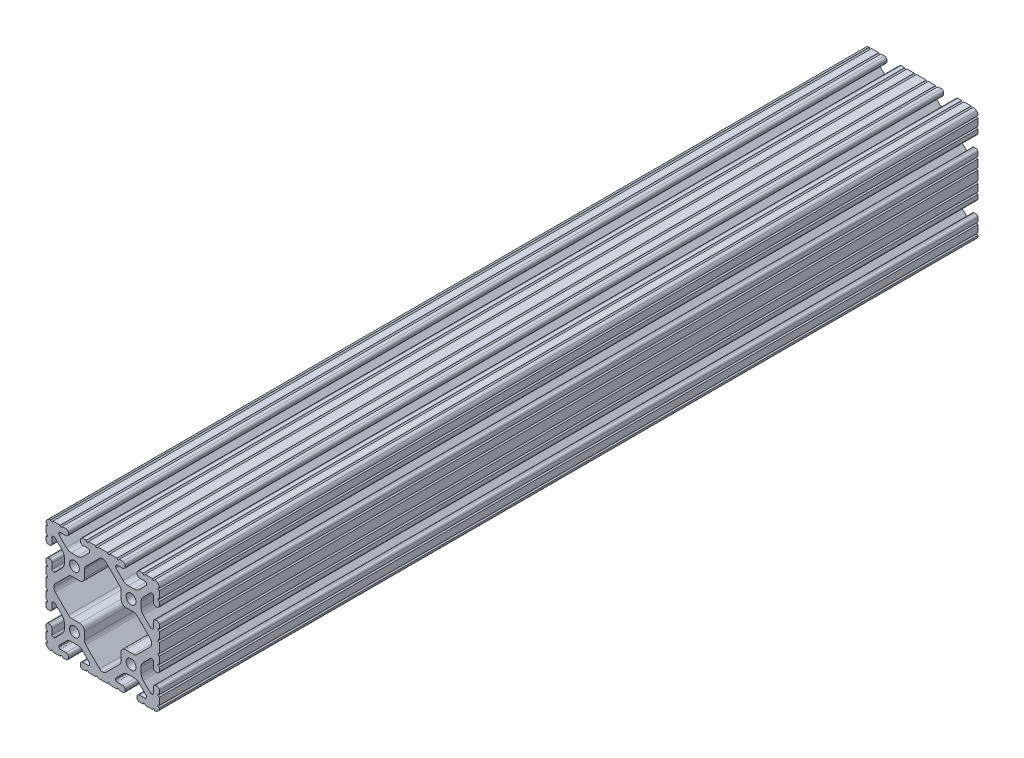
SolidWorks part; units mm, degrees
ref_plane "Front Plane" through (0, 0, 0) normal (0, 0, 1) x (1, 0, 0)
ref_plane "Top Plane" through (0, 0, 0) normal (0, 1, 0) x (1, 0, 0)
ref_plane "Right Plane" through (0, 0, 0) normal (1, 0, 0) x (0, 0, -1)
sketch "Sketch1" plane through (0, 0, 0) normal (0, 0, 1) x (1, 0, 0)
  line L0 (0, 38.1) -> (0, -38.1) construction
  line L1 (-38.1, -38.1) -> (38.1, -38.1) construction
  line L2 (-38.1, -38.1) -> (-38.1, 38.1) construction
  line L3 (-38.1, 38.1) -> (38.1, 38.1) construction
  line L4 (38.1, -38.1) -> (38.1, 38.1) construction
  line L5 (0, 38.1) -> (0, -38.1) construction
  line L6 (-38.1, 0) -> (38.1, 0) construction
  line L7 (-19.05, 19.05) -> (19.05, 19.05) construction
  line L8 (-19.05, 19.05) -> (-19.05, -19.05) construction
  line L9 (-19.05, -19.05) -> (19.05, -19.05) construction
  line L10 (19.05, 19.05) -> (19.05, -19.05) construction
  line L11 (-23.114, 38.1) -> (-23.114, -38.1) construction
  line L12 (-23.114, -38.1) -> (-14.986, 38.1) construction
  line L13 (-14.986, 38.1) -> (-14.986, -38.1) construction
  circle A0 centre (19.05, 19.05) radius 3.3274
  point P0 (0, 0)
  point P9 (0, 0)
  point P12 (-19.05, 0)
  line B0 (-11.3637, -22.8433) -> (-2.0515, -32.1555)
  line B1 (-12.2936, -15.4686) -> (-12.2936, -20.5983)
  line B2 (-20.769, -12.2936) -> (-15.4686, -12.2936)
  line B3 (-31.9021, -2.4756) -> (-23.0141, -11.3637)
  line B4 (-23.0141, 11.3637) -> (-31.9021, 2.4756)
  line B5 (-15.4686, 12.2936) -> (-20.769, 12.2936)
  line B6 (-12.2936, 20.5983) -> (-12.2936, 15.4686)
  line B7 (-2.0515, 32.1555) -> (-11.3637, 22.8433)
  line B8 (11.3637, 22.8433) -> (2.0515, 32.1555)
  line B9 (12.2936, 15.4686) -> (12.2936, 20.5983)
  line B10 (20.769, 12.2936) -> (15.4686, 12.2936)
  line B11 (31.9021, 2.4756) -> (23.0141, 11.3637)
  line B12 (23.0141, -11.3637) -> (31.9021, -2.4756)
  line B13 (15.4686, -12.2936) -> (20.769, -12.2936)
  line B14 (12.2936, -20.5983) -> (12.2936, -15.4686)
  line B15 (2.0515, -32.1555) -> (11.3637, -22.8433)
  line B16 (-4.7773, 38.1) -> (-9.6053, 38.1)
  line B17 (-11.1289, 38.1) -> (-13.4112, 38.1)
  line B18 (-14.986, 36.5252) -> (-14.986, 35.6108)
  line B19 (-13.4112, 34.036) -> (-9.652, 34.036)
  line B20 (-8.763, 33.147) -> (-8.763, 32.4935)
  line B21 (-9.0234, 31.8649) -> (-13.6907, 27.1976)
  line B22 (-17.0493, 25.8064) -> (-21.0507, 25.8064)
  line B23 (-24.4093, 27.1976) -> (-29.1002, 31.8885)
  line B24 (-29.337, 32.7207) -> (-29.337, 33.147)
  line B25 (-28.448, 34.036) -> (-24.6888, 34.036)
  line B26 (-23.114, 35.6108) -> (-23.114, 36.5252)
  line B27 (-24.6888, 38.1) -> (-27.0772, 38.1)
  line B28 (-28.6011, 38.1) -> (-33.4288, 38.1)
  line B29 (-38.1, 33.373) -> (-38.1, 28.5453)
  line B30 (-38.1, 27.0238) -> (-38.1, 24.6302)
  line B31 (-36.5252, 23.0554) -> (-35.6108, 23.0554)
  line B32 (-34.036, 24.6302) -> (-34.036, 28.448)
  line B33 (-33.147, 29.337) -> (-32.6643, 29.337)
  line B34 (-32.0357, 29.0766) -> (-27.1976, 24.2385)
  line B35 (-25.8064, 20.8799) -> (-25.8064, 17.2201)
  line B36 (-27.1976, 13.8615) -> (-31.9489, 9.1101)
  line B37 (-32.7869, 8.763) -> (-33.0603, 8.763)
  line B38 (-34.036, 9.7387) -> (-34.036, 13.4698)
  line B39 (-35.6108, 15.0446) -> (-36.5252, 15.0446)
  line B40 (-38.1, 13.4698) -> (-38.1, 11.075)
  line B41 (-38.1, 9.552) -> (-38.1, 4.7238)
  line B42 (-38.1, 3.2007) -> (-38.1, -3.2007)
  line B43 (-38.1, -4.7238) -> (-38.1, -9.552)
  line B44 (-38.1, -11.075) -> (-38.1, -13.4698)
  line B45 (-36.5252, -15.0446) -> (-35.6108, -15.0446)
  line B46 (-34.036, -13.4698) -> (-34.036, -9.7387)
  line B47 (-33.0603, -8.763) -> (-32.7869, -8.763)
  line B48 (-31.9489, -9.1101) -> (-27.1976, -13.8615)
  line B49 (-25.8064, -17.2201) -> (-25.8064, -20.8799)
  line B50 (-27.1976, -24.2385) -> (-32.0357, -29.0766)
  line B51 (-32.6643, -29.337) -> (-33.147, -29.337)
  line B52 (-34.036, -28.448) -> (-34.036, -24.6302)
  line B53 (-35.6108, -23.0554) -> (-36.5252, -23.0554)
  line B54 (-38.1, -24.6302) -> (-38.1, -27.0238)
  line B55 (-38.1, -28.5453) -> (-38.1, -33.373)
  line B56 (-33.4288, -38.1) -> (-28.6011, -38.1)
  line B57 (-27.0772, -38.1) -> (-24.6888, -38.1)
  line B58 (-23.114, -36.5252) -> (-23.114, -35.6108)
  line B59 (-24.6888, -34.036) -> (-28.448, -34.036)
  line B60 (-29.337, -33.147) -> (-29.337, -32.7207)
  line B61 (-29.1002, -31.8885) -> (-24.4093, -27.1976)
  line B62 (-21.0507, -25.8064) -> (-17.0493, -25.8064)
  line B63 (-13.6907, -27.1976) -> (-9.0234, -31.8649)
  line B64 (-8.763, -32.4935) -> (-8.763, -33.147)
  line B65 (-9.652, -34.036) -> (-13.4112, -34.036)
  line B66 (-14.986, -35.6108) -> (-14.986, -36.5252)
  line B67 (-13.4112, -38.1) -> (-11.1289, -38.1)
  line B68 (-9.6053, -38.1) -> (-4.7773, -38.1)
  line B69 (-3.2537, -38.1) -> (3.2537, -38.1)
  line B70 (4.7773, -38.1) -> (9.6053, -38.1)
  line B71 (11.1289, -38.1) -> (13.4112, -38.1)
  line B72 (14.986, -36.5252) -> (14.986, -35.6108)
  line B73 (13.4112, -34.036) -> (9.652, -34.036)
  line B74 (8.763, -33.147) -> (8.763, -32.4935)
  line B75 (9.0234, -31.8649) -> (13.6907, -27.1976)
  line B76 (17.0493, -25.8064) -> (21.0507, -25.8064)
  line B77 (24.4093, -27.1976) -> (29.1002, -31.8885)
  line B78 (29.337, -32.7207) -> (29.337, -33.147)
  line B79 (28.448, -34.036) -> (24.6888, -34.036)
  line B80 (23.114, -35.6108) -> (23.114, -36.5252)
  line B81 (24.6888, -38.1) -> (27.0772, -38.1)
  line B82 (28.6011, -38.1) -> (33.4288, -38.1)
  line B83 (38.1, -33.373) -> (38.1, -28.5453)
  line B84 (38.1, -27.0238) -> (38.1, -24.6302)
  line B85 (36.5252, -23.0554) -> (35.6108, -23.0554)
  line B86 (34.036, -24.6302) -> (34.036, -28.448)
  line B87 (33.147, -29.337) -> (32.6643, -29.337)
  line B88 (32.0357, -29.0766) -> (27.1976, -24.2385)
  line B89 (25.8064, -20.8799) -> (25.8064, -17.2201)
  line B90 (27.1976, -13.8615) -> (31.9489, -9.1101)
  line B91 (32.7869, -8.763) -> (33.0603, -8.763)
  line B92 (34.036, -9.7387) -> (34.036, -13.4698)
  line B93 (35.6108, -15.0446) -> (36.5252, -15.0446)
  line B94 (38.1, -13.4698) -> (38.1, -11.075)
  line B95 (38.1, -9.552) -> (38.1, -4.7238)
  line B96 (38.1, -3.2007) -> (38.1, 3.2007)
  line B97 (38.1, 4.7238) -> (38.1, 9.552)
  line B98 (38.1, 11.075) -> (38.1, 13.4698)
  line B99 (36.5252, 15.0446) -> (35.6108, 15.0446)
  line B100 (34.036, 13.4698) -> (34.036, 9.7387)
  line B101 (33.0603, 8.763) -> (32.7869, 8.763)
  line B102 (31.9489, 9.1101) -> (27.1976, 13.8615)
  line B103 (25.8064, 17.2201) -> (25.8064, 20.8799)
  line B104 (27.1976, 24.2385) -> (32.0357, 29.0766)
  line B105 (32.6643, 29.337) -> (33.147, 29.337)
  line B106 (34.036, 28.448) -> (34.036, 24.6302)
  line B107 (35.6108, 23.0554) -> (36.5252, 23.0554)
  line B108 (38.1, 24.6302) -> (38.1, 27.0238)
  line B109 (38.1, 28.5453) -> (38.1, 33.373)
  line B110 (33.4288, 38.1) -> (28.6011, 38.1)
  line B111 (27.0772, 38.1) -> (24.6888, 38.1)
  line B112 (23.114, 36.5252) -> (23.114, 35.6108)
  line B113 (24.6888, 34.036) -> (28.448, 34.036)
  line B114 (29.337, 33.147) -> (29.337, 32.7207)
  line B115 (29.1002, 31.8885) -> (24.4093, 27.1976)
  line B116 (21.0507, 25.8064) -> (17.0493, 25.8064)
  line B117 (13.6907, 27.1976) -> (9.0234, 31.8649)
  line B118 (8.763, 32.4935) -> (8.763, 33.147)
  line B119 (9.652, 34.036) -> (13.4112, 34.036)
  line B120 (14.986, 35.6108) -> (14.986, 36.5252)
  line B121 (13.4112, 38.1) -> (11.1289, 38.1)
  line B122 (9.6053, 38.1) -> (4.7773, 38.1)
  line B123 (3.2537, 38.1) -> (-3.2537, 38.1)
  circle B124 centre (-19.05, 19.05) radius 3.3274
  circle B125 centre (-19.05, -19.05) radius 3.3274
  circle B126 centre (19.05, -19.05) radius 3.3274
  circle B127 centre (19.05, 19.05) radius 3.3274
  arc B128 (0, -33.011) -> (2.0515, -32.1555) centre (-0.0139, -30.09) ccw
  arc B129 (-2.0515, -32.1555) -> (0, -33.011) centre (0.0139, -30.09) ccw
  arc B130 (-12.2936, -20.5983) -> (-11.3637, -22.8433) centre (-9.1186, -20.5983) ccw
  arc B131 (-12.2936, -15.4686) -> (-15.4686, -12.2936) centre (-15.4686, -15.4686) ccw
  arc B132 (-23.0141, -11.3637) -> (-20.769, -12.2936) centre (-20.769, -9.1186) ccw
  arc B133 (-32.7287, 0) -> (-31.9021, -2.4756) centre (-29.8367, -0.4102) ccw
  arc B134 (-31.9021, 2.4756) -> (-32.7287, 0) centre (-29.8367, 0.4102) ccw
  arc B135 (-20.769, 12.2936) -> (-23.0141, 11.3637) centre (-20.769, 9.1186) ccw
  arc B136 (-15.4686, 12.2936) -> (-12.2936, 15.4686) centre (-15.4686, 15.4686) ccw
  arc B137 (-11.3637, 22.8433) -> (-12.2936, 20.5983) centre (-9.1186, 20.5983) ccw
  arc B138 (0, 33.011) -> (-2.0515, 32.1555) centre (0.0139, 30.09) ccw
  arc B139 (2.0515, 32.1555) -> (0, 33.011) centre (-0.0139, 30.09) ccw
  arc B140 (12.2936, 20.5983) -> (11.3637, 22.8433) centre (9.1186, 20.5983) ccw
  arc B141 (12.2936, 15.4686) -> (15.4686, 12.2936) centre (15.4686, 15.4686) ccw
  arc B142 (23.0141, 11.3637) -> (20.769, 12.2936) centre (20.769, 9.1186) ccw
  arc B143 (32.7287, 0) -> (31.9021, 2.4756) centre (29.8367, 0.4102) ccw
  arc B144 (31.9021, -2.4756) -> (32.7287, 0) centre (29.8367, -0.4102) ccw
  arc B145 (20.769, -12.2936) -> (23.0141, -11.3637) centre (20.769, -9.1186) ccw
  arc B146 (15.4686, -12.2936) -> (12.2936, -15.4686) centre (15.4686, -15.4686) ccw
  arc B147 (11.3637, -22.8433) -> (12.2936, -20.5983) centre (9.1186, -20.5983) ccw
  arc B148 (-4.7773, 38.1) -> (-3.2537, 38.1) centre (-4.0155, 38.0824) ccw
  arc B149 (-11.1289, 38.1) -> (-9.6053, 38.1) centre (-10.3671, 38.0824) ccw
  arc B150 (-13.4112, 38.1) -> (-14.986, 36.5252) centre (-13.4112, 36.5252) ccw
  arc B151 (-14.986, 35.6108) -> (-13.4112, 34.036) centre (-13.4112, 35.6108) ccw
  arc B152 (-8.763, 33.147) -> (-9.652, 34.036) centre (-9.652, 33.147) ccw
  arc B153 (-9.0234, 31.8649) -> (-8.763, 32.4935) centre (-9.652, 32.4935) ccw
  arc B154 (-17.0493, 25.8064) -> (-13.6907, 27.1976) centre (-17.0493, 30.5562) ccw
  arc B155 (-24.4093, 27.1976) -> (-21.0507, 25.8064) centre (-21.0507, 30.5562) ccw
  arc B156 (-29.337, 32.7207) -> (-29.1002, 31.8885) centre (-28.4716, 32.5172) ccw
  arc B157 (-28.448, 34.036) -> (-29.337, 33.147) centre (-28.448, 33.147) ccw
  arc B158 (-24.6888, 34.036) -> (-23.114, 35.6108) centre (-24.6888, 35.6108) ccw
  arc B159 (-23.114, 36.5252) -> (-24.6888, 38.1) centre (-24.6888, 36.5252) ccw
  arc B160 (-28.6011, 38.1) -> (-27.0772, 38.1) centre (-27.8392, 38.0824) ccw
  arc B161 (-34.9527, 38.1) -> (-33.4288, 38.1) centre (-34.1907, 38.0824) ccw
  arc B162 (-34.9527, 38.1) -> (-37.0861, 37.1826) centre (-34.8521, 34.9266) ccw
  arc B163 (-37.0861, 37.1826) -> (-38.1, 34.8455) centre (-34.925, 34.8566) ccw
  arc B164 (-38.1, 33.373) -> (-38.1, 34.8455) centre (-37.9035, 34.1092) ccw
  arc B165 (-38.1, 27.0238) -> (-38.1, 28.5453) centre (-37.9035, 27.7845) ccw
  arc B166 (-38.1, 24.6302) -> (-36.5252, 23.0554) centre (-36.5252, 24.6302) ccw
  arc B167 (-35.6108, 23.0554) -> (-34.036, 24.6302) centre (-35.6108, 24.6302) ccw
  arc B168 (-33.147, 29.337) -> (-34.036, 28.448) centre (-33.147, 28.448) ccw
  arc B169 (-32.0357, 29.0766) -> (-32.6643, 29.337) centre (-32.6643, 28.448) ccw
  arc B170 (-25.8064, 20.8799) -> (-27.1976, 24.2385) centre (-30.5562, 20.8799) ccw
  arc B171 (-27.1976, 13.8615) -> (-25.8064, 17.2201) centre (-30.5562, 17.2201) ccw
  arc B172 (-32.7869, 8.763) -> (-31.9489, 9.1101) centre (-32.7869, 9.9481) ccw
  arc B173 (-34.036, 9.7387) -> (-33.0603, 8.763) centre (-33.0603, 9.7387) ccw
  arc B174 (-34.036, 13.4698) -> (-35.6108, 15.0446) centre (-35.6108, 13.4698) ccw
  arc B175 (-36.5252, 15.0446) -> (-38.1, 13.4698) centre (-36.5252, 13.4698) ccw
  arc B176 (-38.1, 9.552) -> (-38.1, 11.075) centre (-37.9035, 10.3135) ccw
  arc B177 (-38.1, 3.2007) -> (-38.1, 4.7238) centre (-37.9035, 3.9622) ccw
  arc B178 (-38.1, -4.7238) -> (-38.1, -3.2007) centre (-37.9035, -3.9622) ccw
  arc B179 (-38.1, -11.075) -> (-38.1, -9.552) centre (-37.9035, -10.3135) ccw
  arc B180 (-38.1, -13.4698) -> (-36.5252, -15.0446) centre (-36.5252, -13.4698) ccw
  arc B181 (-35.6108, -15.0446) -> (-34.036, -13.4698) centre (-35.6108, -13.4698) ccw
  arc B182 (-33.0603, -8.763) -> (-34.036, -9.7387) centre (-33.0603, -9.7387) ccw
  arc B183 (-31.9489, -9.1101) -> (-32.7869, -8.763) centre (-32.7869, -9.9481) ccw
  arc B184 (-25.8064, -17.2201) -> (-27.1976, -13.8615) centre (-30.5562, -17.2201) ccw
  arc B185 (-27.1976, -24.2385) -> (-25.8064, -20.8799) centre (-30.5562, -20.8799) ccw
  arc B186 (-32.6643, -29.337) -> (-32.0357, -29.0766) centre (-32.6643, -28.448) ccw
  arc B187 (-34.036, -28.448) -> (-33.147, -29.337) centre (-33.147, -28.448) ccw
  arc B188 (-34.036, -24.6302) -> (-35.6108, -23.0554) centre (-35.6108, -24.6302) ccw
  arc B189 (-36.5252, -23.0554) -> (-38.1, -24.6302) centre (-36.5252, -24.6302) ccw
  arc B190 (-38.1, -28.5453) -> (-38.1, -27.0238) centre (-37.9035, -27.7845) ccw
  arc B191 (-38.1, -34.8455) -> (-38.1, -33.373) centre (-37.9035, -34.1092) ccw
  arc B192 (-38.1, -34.8455) -> (-37.0861, -37.1826) centre (-34.925, -34.8566) ccw
  arc B193 (-37.0861, -37.1826) -> (-34.9527, -38.1) centre (-34.8521, -34.9266) ccw
  arc B194 (-33.4288, -38.1) -> (-34.9527, -38.1) centre (-34.1907, -38.0824) ccw
  arc B195 (-27.0772, -38.1) -> (-28.6011, -38.1) centre (-27.8392, -38.0824) ccw
  arc B196 (-24.6888, -38.1) -> (-23.114, -36.5252) centre (-24.6888, -36.5252) ccw
  arc B197 (-23.114, -35.6108) -> (-24.6888, -34.036) centre (-24.6888, -35.6108) ccw
  arc B198 (-29.337, -33.147) -> (-28.448, -34.036) centre (-28.448, -33.147) ccw
  arc B199 (-29.1002, -31.8885) -> (-29.337, -32.7207) centre (-28.4716, -32.5172) ccw
  arc B200 (-21.0507, -25.8064) -> (-24.4093, -27.1976) centre (-21.0507, -30.5562) ccw
  arc B201 (-13.6907, -27.1976) -> (-17.0493, -25.8064) centre (-17.0493, -30.5562) ccw
  arc B202 (-8.763, -32.4935) -> (-9.0234, -31.8649) centre (-9.652, -32.4935) ccw
  arc B203 (-9.652, -34.036) -> (-8.763, -33.147) centre (-9.652, -33.147) ccw
  arc B204 (-13.4112, -34.036) -> (-14.986, -35.6108) centre (-13.4112, -35.6108) ccw
  arc B205 (-14.986, -36.5252) -> (-13.4112, -38.1) centre (-13.4112, -36.5252) ccw
  arc B206 (-9.6053, -38.1) -> (-11.1289, -38.1) centre (-10.3671, -38.0824) ccw
  arc B207 (-3.2537, -38.1) -> (-4.7773, -38.1) centre (-4.0155, -38.0824) ccw
  arc B208 (4.7773, -38.1) -> (3.2537, -38.1) centre (4.0155, -38.0824) ccw
  arc B209 (11.1289, -38.1) -> (9.6053, -38.1) centre (10.3671, -38.0824) ccw
  arc B210 (13.4112, -38.1) -> (14.986, -36.5252) centre (13.4112, -36.5252) ccw
  arc B211 (14.986, -35.6108) -> (13.4112, -34.036) centre (13.4112, -35.6108) ccw
  arc B212 (8.763, -33.147) -> (9.652, -34.036) centre (9.652, -33.147) ccw
  arc B213 (9.0234, -31.8649) -> (8.763, -32.4935) centre (9.652, -32.4935) ccw
  arc B214 (17.0493, -25.8064) -> (13.6907, -27.1976) centre (17.0493, -30.5562) ccw
  arc B215 (24.4093, -27.1976) -> (21.0507, -25.8064) centre (21.0507, -30.5562) ccw
  arc B216 (29.337, -32.7207) -> (29.1002, -31.8885) centre (28.4716, -32.5172) ccw
  arc B217 (28.448, -34.036) -> (29.337, -33.147) centre (28.448, -33.147) ccw
  arc B218 (24.6888, -34.036) -> (23.114, -35.6108) centre (24.6888, -35.6108) ccw
  arc B219 (23.114, -36.5252) -> (24.6888, -38.1) centre (24.6888, -36.5252) ccw
  arc B220 (28.6011, -38.1) -> (27.0772, -38.1) centre (27.8392, -38.0824) ccw
  arc B221 (34.9527, -38.1) -> (33.4288, -38.1) centre (34.1907, -38.0824) ccw
  arc B222 (34.9527, -38.1) -> (37.0861, -37.1826) centre (34.8521, -34.9266) ccw
  arc B223 (37.0861, -37.1826) -> (38.1, -34.8455) centre (34.925, -34.8566) ccw
  arc B224 (38.1, -33.373) -> (38.1, -34.8455) centre (37.9035, -34.1092) ccw
  arc B225 (38.1, -27.0238) -> (38.1, -28.5453) centre (37.9035, -27.7845) ccw
  arc B226 (38.1, -24.6302) -> (36.5252, -23.0554) centre (36.5252, -24.6302) ccw
  arc B227 (35.6108, -23.0554) -> (34.036, -24.6302) centre (35.6108, -24.6302) ccw
  arc B228 (33.147, -29.337) -> (34.036, -28.448) centre (33.147, -28.448) ccw
  arc B229 (32.0357, -29.0766) -> (32.6643, -29.337) centre (32.6643, -28.448) ccw
  arc B230 (25.8064, -20.8799) -> (27.1976, -24.2385) centre (30.5562, -20.8799) ccw
  arc B231 (27.1976, -13.8615) -> (25.8064, -17.2201) centre (30.5562, -17.2201) ccw
  arc B232 (32.7869, -8.763) -> (31.9489, -9.1101) centre (32.7869, -9.9481) ccw
  arc B233 (34.036, -9.7387) -> (33.0603, -8.763) centre (33.0603, -9.7387) ccw
  arc B234 (34.036, -13.4698) -> (35.6108, -15.0446) centre (35.6108, -13.4698) ccw
  arc B235 (36.5252, -15.0446) -> (38.1, -13.4698) centre (36.5252, -13.4698) ccw
  arc B236 (38.1, -9.552) -> (38.1, -11.075) centre (37.9035, -10.3135) ccw
  arc B237 (38.1, -3.2007) -> (38.1, -4.7238) centre (37.9035, -3.9622) ccw
  arc B238 (38.1, 4.7238) -> (38.1, 3.2007) centre (37.9035, 3.9622) ccw
  arc B239 (38.1, 11.075) -> (38.1, 9.552) centre (37.9035, 10.3135) ccw
  arc B240 (38.1, 13.4698) -> (36.5252, 15.0446) centre (36.5252, 13.4698) ccw
  arc B241 (35.6108, 15.0446) -> (34.036, 13.4698) centre (35.6108, 13.4698) ccw
  arc B242 (33.0603, 8.763) -> (34.036, 9.7387) centre (33.0603, 9.7387) ccw
  arc B243 (31.9489, 9.1101) -> (32.7869, 8.763) centre (32.7869, 9.9481) ccw
  arc B244 (25.8064, 17.2201) -> (27.1976, 13.8615) centre (30.5562, 17.2201) ccw
  arc B245 (27.1976, 24.2385) -> (25.8064, 20.8799) centre (30.5562, 20.8799) ccw
  arc B246 (32.6643, 29.337) -> (32.0357, 29.0766) centre (32.6643, 28.448) ccw
  arc B247 (34.036, 28.448) -> (33.147, 29.337) centre (33.147, 28.448) ccw
  arc B248 (34.036, 24.6302) -> (35.6108, 23.0554) centre (35.6108, 24.6302) ccw
  arc B249 (36.5252, 23.0554) -> (38.1, 24.6302) centre (36.5252, 24.6302) ccw
  arc B250 (38.1, 28.5453) -> (38.1, 27.0238) centre (37.9035, 27.7845) ccw
  arc B251 (38.1, 34.8455) -> (38.1, 33.373) centre (37.9035, 34.1092) ccw
  arc B252 (38.1, 34.8455) -> (37.0861, 37.1826) centre (34.925, 34.8566) ccw
  arc B253 (37.0861, 37.1826) -> (34.9527, 38.1) centre (34.8521, 34.9266) ccw
  arc B254 (33.4288, 38.1) -> (34.9527, 38.1) centre (34.1907, 38.0824) ccw
  arc B255 (27.0772, 38.1) -> (28.6011, 38.1) centre (27.8392, 38.0824) ccw
  arc B256 (24.6888, 38.1) -> (23.114, 36.5252) centre (24.6888, 36.5252) ccw
  arc B257 (23.114, 35.6108) -> (24.6888, 34.036) centre (24.6888, 35.6108) ccw
  arc B258 (29.337, 33.147) -> (28.448, 34.036) centre (28.448, 33.147) ccw
  arc B259 (29.1002, 31.8885) -> (29.337, 32.7207) centre (28.4716, 32.5172) ccw
  arc B260 (21.0507, 25.8064) -> (24.4093, 27.1976) centre (21.0507, 30.5562) ccw
  arc B261 (13.6907, 27.1976) -> (17.0493, 25.8064) centre (17.0493, 30.5562) ccw
  arc B262 (8.763, 32.4935) -> (9.0234, 31.8649) centre (9.652, 32.4935) ccw
  arc B263 (9.652, 34.036) -> (8.763, 33.147) centre (9.652, 33.147) ccw
  arc B264 (13.4112, 34.036) -> (14.986, 35.6108) centre (13.4112, 35.6108) ccw
  arc B265 (14.986, 36.5252) -> (13.4112, 38.1) centre (13.4112, 36.5252) ccw
  arc B266 (9.6053, 38.1) -> (11.1289, 38.1) centre (10.3671, 38.0824) ccw
  arc B267 (3.2537, 38.1) -> (4.7773, 38.1) centre (4.0155, 38.0824) ccw
  dimension "Center Hole Diameter" = 6.6548
  dimension "Rail Width" = 76.2
  dimension "Rail Height" = 76.2
  dimension "T-Slot Width" = 8.128
sketch_block_instance "Block1-1"
sketch_block "Block1"
sketch "Sketch2" plane through (0, 0, 0) normal (1, 0, 0) x (0, 0, -1)
  line L0 (-275, 0) -> (275, 0) construction
  line L1 (-275, 38.1) -> (-275, -38.1) construction
  line L2 (-275, -38.1) -> (275, -38.1) construction
  line L3 (275, -38.1) -> (275, 38.1) construction
  line L4 (-173.4, 0) -> (-173.4, 38.1) construction
  line L5 (-173.4, 38.1) -> (173.4, 38.1) construction
  line L6 (173.4, 38.1) -> (173.4, 0) construction
  point P5 (173.4, 0)
  point P10 (-173.4, 0)
  dimension "D1" = 101.6
  dimension "Length" = 550
  dimension "D2" = 101.6
sketch "Sketch3" plane through (0, 0, 0) normal (0, 0, 1) x (1, 0, 0)
  line L0 (-11.3637, -22.8433) -> (-2.0515, -32.1555) construction
  line L1 (-12.2936, -15.4686) -> (-12.2936, -20.5983) construction
  line L2 (-20.769, -12.2936) -> (-15.4686, -12.2936) construction
  line L3 (-31.9021, -2.4756) -> (-23.0141, -11.3637) construction
  line L4 (-23.0141, 11.3637) -> (-31.9021, 2.4756) construction
  line L5 (-15.4686, 12.2936) -> (-20.769, 12.2936) construction
  line L6 (-12.2936, 20.5983) -> (-12.2936, 15.4686) construction
  line L7 (-2.0515, 32.1555) -> (-11.3637, 22.8433) construction
  line L8 (11.3637, 22.8433) -> (2.0515, 32.1555) construction
  line L9 (12.2936, 15.4686) -> (12.2936, 20.5983) construction
  line L10 (20.769, 12.2936) -> (15.4686, 12.2936) construction
  line L11 (31.9021, 2.4756) -> (23.0141, 11.3637) construction
  line L12 (23.0141, -11.3637) -> (31.9021, -2.4756) construction
  line L13 (15.4686, -12.2936) -> (20.769, -12.2936) construction
  line L14 (12.2936, -20.5983) -> (12.2936, -15.4686) construction
  line L15 (2.0515, -32.1555) -> (11.3637, -22.8433) construction
  line L16 (34.036, 28.448) -> (34.036, 24.6302) construction
  line L17 (35.6108, 23.0554) -> (36.5252, 23.0554) construction
  line L18 (38.1, 24.6302) -> (38.1, 27.0238) construction
  line L19 (38.1, 28.5453) -> (38.1, 33.373) construction
  line L20 (33.4288, 38.1) -> (28.6011, 38.1) construction
  line L21 (27.0772, 38.1) -> (24.6888, 38.1) construction
  line L22 (23.114, 36.5252) -> (23.114, 35.6108) construction
  line L23 (24.6888, 34.036) -> (28.448, 34.036) construction
  line L24 (29.337, 33.147) -> (29.337, 32.7207) construction
  line L25 (29.1002, 31.8885) -> (24.4093, 27.1976) construction
  line L26 (21.0507, 25.8064) -> (17.0493, 25.8064) construction
  line L27 (13.6907, 27.1976) -> (9.0234, 31.8649) construction
  line L28 (8.763, 32.4935) -> (8.763, 33.147) construction
  line L29 (9.652, 34.036) -> (13.4112, 34.036) construction
  line L30 (14.986, 35.6108) -> (14.986, 36.5252) construction
  line L31 (13.4112, 38.1) -> (11.1289, 38.1) construction
  line L32 (9.6053, 38.1) -> (4.7773, 38.1) construction
  line L33 (3.2537, 38.1) -> (-3.2537, 38.1) construction
  line L34 (-4.7773, 38.1) -> (-9.6053, 38.1) construction
  line L35 (-11.1289, 38.1) -> (-13.4112, 38.1) construction
  line L36 (-14.986, 36.5252) -> (-14.986, 35.6108) construction
  line L37 (-13.4112, 34.036) -> (-9.652, 34.036) construction
  line L38 (-8.763, 33.147) -> (-8.763, 32.4935) construction
  line L39 (-9.0234, 31.8649) -> (-13.6907, 27.1976) construction
  line L40 (-17.0493, 25.8064) -> (-21.0507, 25.8064) construction
  line L41 (-24.4093, 27.1976) -> (-29.1002, 31.8885) construction
  line L42 (-29.337, 32.7207) -> (-29.337, 33.147) construction
  line L43 (-28.448, 34.036) -> (-24.6888, 34.036) construction
  line L44 (-23.114, 35.6108) -> (-23.114, 36.5252) construction
  line L45 (-24.6888, 38.1) -> (-27.0772, 38.1) construction
  line L46 (-28.6011, 38.1) -> (-33.4288, 38.1) construction
  line L47 (-38.1, 33.373) -> (-38.1, 28.5453) construction
  line L48 (-38.1, 27.0238) -> (-38.1, 24.6302) construction
  line L49 (-36.5252, 23.0554) -> (-35.6108, 23.0554) construction
  line L50 (-34.036, 24.6302) -> (-34.036, 28.448) construction
  line L51 (-33.147, 29.337) -> (-32.6643, 29.337) construction
  line L52 (-32.0357, 29.0766) -> (-27.1976, 24.2385) construction
  line L53 (-25.8064, 20.8799) -> (-25.8064, 17.2201) construction
  line L54 (-27.1976, 13.8615) -> (-31.9489, 9.1101) construction
  line L55 (-32.7869, 8.763) -> (-33.0603, 8.763) construction
  line L56 (-34.036, 9.7387) -> (-34.036, 13.4698) construction
  line L57 (-35.6108, 15.0446) -> (-36.5252, 15.0446) construction
  line L58 (-38.1, 13.4698) -> (-38.1, 11.075) construction
  line L59 (-38.1, 9.552) -> (-38.1, 4.7238) construction
  line L60 (-38.1, 3.2007) -> (-38.1, -3.2007) construction
  line L61 (-38.1, -4.7238) -> (-38.1, -9.552) construction
  line L62 (-38.1, -11.075) -> (-38.1, -13.4698) construction
  line L63 (-36.5252, -15.0446) -> (-35.6108, -15.0446) construction
  line L64 (-34.036, -13.4698) -> (-34.036, -9.7387) construction
  line L65 (-33.0603, -8.763) -> (-32.7869, -8.763) construction
  line L66 (-31.9489, -9.1101) -> (-27.1976, -13.8615) construction
  line L67 (-25.8064, -17.2201) -> (-25.8064, -20.8799) construction
  line L68 (-27.1976, -24.2385) -> (-32.0357, -29.0766) construction
  line L69 (-32.6643, -29.337) -> (-33.147, -29.337) construction
  line L70 (-34.036, -28.448) -> (-34.036, -24.6302) construction
  line L71 (-35.6108, -23.0554) -> (-36.5252, -23.0554) construction
  line L72 (-38.1, -24.6302) -> (-38.1, -27.0238) construction
  line L73 (-38.1, -28.5453) -> (-38.1, -33.373) construction
  line L74 (-33.4288, -38.1) -> (-28.6011, -38.1) construction
  line L75 (-27.0772, -38.1) -> (-24.6888, -38.1) construction
  line L76 (-23.114, -36.5252) -> (-23.114, -35.6108) construction
  line L77 (-24.6888, -34.036) -> (-28.448, -34.036) construction
  line L78 (-29.337, -33.147) -> (-29.337, -32.7207) construction
  line L79 (-29.1002, -31.8885) -> (-24.4093, -27.1976) construction
  line L80 (-21.0507, -25.8064) -> (-17.0493, -25.8064) construction
  line L81 (-13.6907, -27.1976) -> (-9.0234, -31.8649) construction
  line L82 (-8.763, -32.4935) -> (-8.763, -33.147) construction
  line L83 (-9.652, -34.036) -> (-13.4112, -34.036) construction
  line L84 (-14.986, -35.6108) -> (-14.986, -36.5252) construction
  line L85 (-13.4112, -38.1) -> (-11.1289, -38.1) construction
  line L86 (-9.6053, -38.1) -> (-4.7773, -38.1) construction
  line L87 (-3.2537, -38.1) -> (3.2537, -38.1) construction
  line L88 (4.7773, -38.1) -> (9.6053, -38.1) construction
  line L89 (11.1289, -38.1) -> (13.4112, -38.1) construction
  line L90 (14.986, -36.5252) -> (14.986, -35.6108) construction
  line L91 (13.4112, -34.036) -> (9.652, -34.036) construction
  line L92 (8.763, -33.147) -> (8.763, -32.4935) construction
  line L93 (9.0234, -31.8649) -> (13.6907, -27.1976) construction
  line L94 (17.0493, -25.8064) -> (21.0507, -25.8064) construction
  line L95 (24.4093, -27.1976) -> (29.1002, -31.8885) construction
  line L96 (29.337, -32.7207) -> (29.337, -33.147) construction
  line L97 (28.448, -34.036) -> (24.6888, -34.036) construction
  line L98 (23.114, -35.6108) -> (23.114, -36.5252) construction
  line L99 (24.6888, -38.1) -> (27.0772, -38.1) construction
  line L100 (28.6011, -38.1) -> (33.4288, -38.1) construction
  line L101 (38.1, -33.373) -> (38.1, -28.5453) construction
  line L102 (38.1, -27.0238) -> (38.1, -24.6302) construction
  line L103 (36.5252, -23.0554) -> (35.6108, -23.0554) construction
  line L104 (34.036, -24.6302) -> (34.036, -28.448) construction
  line L105 (33.147, -29.337) -> (32.6643, -29.337) construction
  line L106 (32.0357, -29.0766) -> (27.1976, -24.2385) construction
  line L107 (25.8064, -20.8799) -> (25.8064, -17.2201) construction
  line L108 (27.1976, -13.8615) -> (31.9489, -9.1101) construction
  line L109 (32.7869, -8.763) -> (33.0603, -8.763) construction
  line L110 (34.036, -9.7387) -> (34.036, -13.4698) construction
  line L111 (35.6108, -15.0446) -> (36.5252, -15.0446) construction
  line L112 (38.1, -13.4698) -> (38.1, -11.075) construction
  line L113 (38.1, -9.552) -> (38.1, -4.7238) construction
  line L114 (38.1, -3.2007) -> (38.1, 3.2007) construction
  line L115 (38.1, 4.7238) -> (38.1, 9.552) construction
  line L116 (38.1, 11.075) -> (38.1, 13.4698) construction
  line L117 (36.5252, 15.0446) -> (35.6108, 15.0446) construction
  line L118 (34.036, 13.4698) -> (34.036, 9.7387) construction
  line L119 (33.0603, 8.763) -> (32.7869, 8.763) construction
  line L120 (31.9489, 9.1101) -> (27.1976, 13.8615) construction
  line L121 (25.8064, 17.2201) -> (25.8064, 20.8799) construction
  line L122 (27.1976, 24.2385) -> (32.0357, 29.0766) construction
  line L123 (32.6643, 29.337) -> (33.147, 29.337) construction
  line L124 (-11.3637, -22.8433) -> (-2.0515, -32.1555)
  line L125 (-12.2936, -15.4686) -> (-12.2936, -20.5983)
  line L126 (-20.769, -12.2936) -> (-15.4686, -12.2936)
  line L127 (-31.9021, -2.4756) -> (-23.0141, -11.3637)
  line L128 (-23.0141, 11.3637) -> (-31.9021, 2.4756)
  line L129 (-15.4686, 12.2936) -> (-20.769, 12.2936)
  line L130 (-12.2936, 20.5983) -> (-12.2936, 15.4686)
  line L131 (-2.0515, 32.1555) -> (-11.3637, 22.8433)
  line L132 (11.3637, 22.8433) -> (2.0515, 32.1555)
  line L133 (12.2936, 15.4686) -> (12.2936, 20.5983)
  line L134 (20.769, 12.2936) -> (15.4686, 12.2936)
  line L135 (31.9021, 2.4756) -> (23.0141, 11.3637)
  line L136 (23.0141, -11.3637) -> (31.9021, -2.4756)
  line L137 (15.4686, -12.2936) -> (20.769, -12.2936)
  line L138 (12.2936, -20.5983) -> (12.2936, -15.4686)
  line L139 (2.0515, -32.1555) -> (11.3637, -22.8433)
  line L140 (34.036, 28.448) -> (34.036, 24.6302)
  line L141 (35.6108, 23.0554) -> (36.5252, 23.0554)
  line L142 (38.1, 24.6302) -> (38.1, 27.0238)
  line L143 (38.1, 28.5453) -> (38.1, 33.373)
  line L144 (33.4288, 38.1) -> (28.6011, 38.1)
  line L145 (27.0772, 38.1) -> (24.6888, 38.1)
  line L146 (23.114, 36.5252) -> (23.114, 35.6108)
  line L147 (24.6888, 34.036) -> (28.448, 34.036)
  line L148 (29.337, 33.147) -> (29.337, 32.7207)
  line L149 (29.1002, 31.8885) -> (24.4093, 27.1976)
  line L150 (21.0507, 25.8064) -> (17.0493, 25.8064)
  line L151 (13.6907, 27.1976) -> (9.0234, 31.8649)
  line L152 (8.763, 32.4935) -> (8.763, 33.147)
  line L153 (9.652, 34.036) -> (13.4112, 34.036)
  line L154 (14.986, 35.6108) -> (14.986, 36.5252)
  line L155 (13.4112, 38.1) -> (11.1289, 38.1)
  line L156 (9.6053, 38.1) -> (4.7773, 38.1)
  line L157 (3.2537, 38.1) -> (-3.2537, 38.1)
  line L158 (-4.7773, 38.1) -> (-9.6053, 38.1)
  line L159 (-11.1289, 38.1) -> (-13.4112, 38.1)
  line L160 (-14.986, 36.5252) -> (-14.986, 35.6108)
  line L161 (-13.4112, 34.036) -> (-9.652, 34.036)
  line L162 (-8.763, 33.147) -> (-8.763, 32.4935)
  line L163 (-9.0234, 31.8649) -> (-13.6907, 27.1976)
  line L164 (-17.0493, 25.8064) -> (-21.0507, 25.8064)
  line L165 (-24.4093, 27.1976) -> (-29.1002, 31.8885)
  line L166 (-29.337, 32.7207) -> (-29.337, 33.147)
  line L167 (-28.448, 34.036) -> (-24.6888, 34.036)
  line L168 (-23.114, 35.6108) -> (-23.114, 36.5252)
  line L169 (-24.6888, 38.1) -> (-27.0772, 38.1)
  line L170 (-28.6011, 38.1) -> (-33.4288, 38.1)
  line L171 (-38.1, 33.373) -> (-38.1, 28.5453)
  line L172 (-38.1, 27.0238) -> (-38.1, 24.6302)
  line L173 (-36.5252, 23.0554) -> (-35.6108, 23.0554)
  line L174 (-34.036, 24.6302) -> (-34.036, 28.448)
  line L175 (-33.147, 29.337) -> (-32.6643, 29.337)
  line L176 (-32.0357, 29.0766) -> (-27.1976, 24.2385)
  line L177 (-25.8064, 20.8799) -> (-25.8064, 17.2201)
  line L178 (-27.1976, 13.8615) -> (-31.9489, 9.1101)
  line L179 (-32.7869, 8.763) -> (-33.0603, 8.763)
  line L180 (-34.036, 9.7387) -> (-34.036, 13.4698)
  line L181 (-35.6108, 15.0446) -> (-36.5252, 15.0446)
  line L182 (-38.1, 13.4698) -> (-38.1, 11.075)
  line L183 (-38.1, 9.552) -> (-38.1, 4.7238)
  line L184 (-38.1, 3.2007) -> (-38.1, -3.2007)
  line L185 (-38.1, -4.7238) -> (-38.1, -9.552)
  line L186 (-38.1, -11.075) -> (-38.1, -13.4698)
  line L187 (-36.5252, -15.0446) -> (-35.6108, -15.0446)
  line L188 (-34.036, -13.4698) -> (-34.036, -9.7387)
  line L189 (-33.0603, -8.763) -> (-32.7869, -8.763)
  line L190 (-31.9489, -9.1101) -> (-27.1976, -13.8615)
  line L191 (-25.8064, -17.2201) -> (-25.8064, -20.8799)
  line L192 (-27.1976, -24.2385) -> (-32.0357, -29.0766)
  line L193 (-32.6643, -29.337) -> (-33.147, -29.337)
  line L194 (-34.036, -28.448) -> (-34.036, -24.6302)
  line L195 (-35.6108, -23.0554) -> (-36.5252, -23.0554)
  line L196 (-38.1, -24.6302) -> (-38.1, -27.0238)
  line L197 (-38.1, -28.5453) -> (-38.1, -33.373)
  line L198 (-33.4288, -38.1) -> (-28.6011, -38.1)
  line L199 (-27.0772, -38.1) -> (-24.6888, -38.1)
  line L200 (-23.114, -36.5252) -> (-23.114, -35.6108)
  line L201 (-24.6888, -34.036) -> (-28.448, -34.036)
  line L202 (-29.337, -33.147) -> (-29.337, -32.7207)
  line L203 (-29.1002, -31.8885) -> (-24.4093, -27.1976)
  line L204 (-21.0507, -25.8064) -> (-17.0493, -25.8064)
  line L205 (-13.6907, -27.1976) -> (-9.0234, -31.8649)
  line L206 (-8.763, -32.4935) -> (-8.763, -33.147)
  line L207 (-9.652, -34.036) -> (-13.4112, -34.036)
  line L208 (-14.986, -35.6108) -> (-14.986, -36.5252)
  line L209 (-13.4112, -38.1) -> (-11.1289, -38.1)
  line L210 (-9.6053, -38.1) -> (-4.7773, -38.1)
  line L211 (-3.2537, -38.1) -> (3.2537, -38.1)
  line L212 (4.7773, -38.1) -> (9.6053, -38.1)
  line L213 (11.1289, -38.1) -> (13.4112, -38.1)
  line L214 (14.986, -36.5252) -> (14.986, -35.6108)
  line L215 (13.4112, -34.036) -> (9.652, -34.036)
  line L216 (8.763, -33.147) -> (8.763, -32.4935)
  line L217 (9.0234, -31.8649) -> (13.6907, -27.1976)
  line L218 (17.0493, -25.8064) -> (21.0507, -25.8064)
  line L219 (24.4093, -27.1976) -> (29.1002, -31.8885)
  line L220 (29.337, -32.7207) -> (29.337, -33.147)
  line L221 (28.448, -34.036) -> (24.6888, -34.036)
  line L222 (23.114, -35.6108) -> (23.114, -36.5252)
  line L223 (24.6888, -38.1) -> (27.0772, -38.1)
  line L224 (28.6011, -38.1) -> (33.4288, -38.1)
  line L225 (38.1, -33.373) -> (38.1, -28.5453)
  line L226 (38.1, -27.0238) -> (38.1, -24.6302)
  line L227 (36.5252, -23.0554) -> (35.6108, -23.0554)
  line L228 (34.036, -24.6302) -> (34.036, -28.448)
  line L229 (33.147, -29.337) -> (32.6643, -29.337)
  line L230 (32.0357, -29.0766) -> (27.1976, -24.2385)
  line L231 (25.8064, -20.8799) -> (25.8064, -17.2201)
  line L232 (27.1976, -13.8615) -> (31.9489, -9.1101)
  line L233 (32.7869, -8.763) -> (33.0603, -8.763)
  line L234 (34.036, -9.7387) -> (34.036, -13.4698)
  line L235 (35.6108, -15.0446) -> (36.5252, -15.0446)
  line L236 (38.1, -13.4698) -> (38.1, -11.075)
  line L237 (38.1, -9.552) -> (38.1, -4.7238)
  line L238 (38.1, -3.2007) -> (38.1, 3.2007)
  line L239 (38.1, 4.7238) -> (38.1, 9.552)
  line L240 (38.1, 11.075) -> (38.1, 13.4698)
  line L241 (36.5252, 15.0446) -> (35.6108, 15.0446)
  line L242 (34.036, 13.4698) -> (34.036, 9.7387)
  line L243 (33.0603, 8.763) -> (32.7869, 8.763)
  line L244 (31.9489, 9.1101) -> (27.1976, 13.8615)
  line L245 (25.8064, 17.2201) -> (25.8064, 20.8799)
  line L246 (27.1976, 24.2385) -> (32.0357, 29.0766)
  line L247 (32.6643, 29.337) -> (33.147, 29.337)
  arc A0 (-2.0515, -32.1555) -> (0, -33.011) centre (0.0139, -30.09) ccw construction
  circle A1 centre (19.05, 19.05) radius 3.3274
  circle A2 centre (19.05, 19.05) radius 3.3274
  arc A3 (-12.2936, -20.5983) -> (-11.3637, -22.8433) centre (-9.1186, -20.5983) ccw construction
  arc A4 (-12.2936, -15.4686) -> (-15.4686, -12.2936) centre (-15.4686, -15.4686) ccw construction
  arc A5 (-23.0141, -11.3637) -> (-20.769, -12.2936) centre (-20.769, -9.1186) ccw construction
  arc A6 (-32.7287, 0) -> (-31.9021, -2.4756) centre (-29.8367, -0.4102) ccw construction
  arc A7 (-31.9021, 2.4756) -> (-32.7287, 0) centre (-29.8367, 0.4102) ccw construction
  arc A8 (-20.769, 12.2936) -> (-23.0141, 11.3637) centre (-20.769, 9.1186) ccw construction
  arc A9 (-15.4686, 12.2936) -> (-12.2936, 15.4686) centre (-15.4686, 15.4686) ccw construction
  arc A10 (-11.3637, 22.8433) -> (-12.2936, 20.5983) centre (-9.1186, 20.5983) ccw construction
  arc A11 (0, 33.011) -> (-2.0515, 32.1555) centre (0.0139, 30.09) ccw construction
  arc A12 (2.0515, 32.1555) -> (0, 33.011) centre (-0.0139, 30.09) ccw construction
  arc A13 (12.2936, 20.5983) -> (11.3637, 22.8433) centre (9.1186, 20.5983) ccw construction
  arc A14 (12.2936, 15.4686) -> (15.4686, 12.2936) centre (15.4686, 15.4686) ccw construction
  arc A15 (23.0141, 11.3637) -> (20.769, 12.2936) centre (20.769, 9.1186) ccw construction
  arc A16 (32.7287, 0) -> (31.9021, 2.4756) centre (29.8367, 0.4102) ccw construction
  arc A17 (31.9021, -2.4756) -> (32.7287, 0) centre (29.8367, -0.4102) ccw construction
  arc A18 (20.769, -12.2936) -> (23.0141, -11.3637) centre (20.769, -9.1186) ccw construction
  arc A19 (15.4686, -12.2936) -> (12.2936, -15.4686) centre (15.4686, -15.4686) ccw construction
  arc A20 (11.3637, -22.8433) -> (12.2936, -20.5983) centre (9.1186, -20.5983) ccw construction
  arc A21 (0, -33.011) -> (2.0515, -32.1555) centre (-0.0139, -30.09) ccw construction
  circle A22 centre (-19.05, 19.05) radius 3.3274 construction
  circle A23 centre (19.05, -19.05) radius 3.3274 construction
  circle A24 centre (-19.05, -19.05) radius 3.3274 construction
  circle A25 centre (19.05, 19.05) radius 3.3274 construction
  arc A26 (34.036, 24.6302) -> (35.6108, 23.0554) centre (35.6108, 24.6302) ccw construction
  arc A27 (36.5252, 23.0554) -> (38.1, 24.6302) centre (36.5252, 24.6302) ccw construction
  arc A28 (38.1, 28.5453) -> (38.1, 27.0238) centre (37.9035, 27.7845) ccw construction
  arc A29 (38.1, 34.8455) -> (38.1, 33.373) centre (37.9035, 34.1092) ccw construction
  arc A30 (38.1, 34.8455) -> (37.0861, 37.1826) centre (34.925, 34.8566) ccw construction
  arc A31 (37.0861, 37.1826) -> (34.9527, 38.1) centre (34.8521, 34.9266) ccw construction
  arc A32 (33.4288, 38.1) -> (34.9527, 38.1) centre (34.1907, 38.0824) ccw construction
  arc A33 (27.0772, 38.1) -> (28.6011, 38.1) centre (27.8392, 38.0824) ccw construction
  arc A34 (24.6888, 38.1) -> (23.114, 36.5252) centre (24.6888, 36.5252) ccw construction
  arc A35 (23.114, 35.6108) -> (24.6888, 34.036) centre (24.6888, 35.6108) ccw construction
  arc A36 (29.337, 33.147) -> (28.448, 34.036) centre (28.448, 33.147) ccw construction
  arc A37 (29.1002, 31.8885) -> (29.337, 32.7207) centre (28.4716, 32.5172) ccw construction
  arc A38 (21.0507, 25.8064) -> (24.4093, 27.1976) centre (21.0507, 30.5562) ccw construction
  arc A39 (13.6907, 27.1976) -> (17.0493, 25.8064) centre (17.0493, 30.5562) ccw construction
  arc A40 (8.763, 32.4935) -> (9.0234, 31.8649) centre (9.652, 32.4935) ccw construction
  arc A41 (9.652, 34.036) -> (8.763, 33.147) centre (9.652, 33.147) ccw construction
  arc A42 (13.4112, 34.036) -> (14.986, 35.6108) centre (13.4112, 35.6108) ccw construction
  arc A43 (14.986, 36.5252) -> (13.4112, 38.1) centre (13.4112, 36.5252) ccw construction
  arc A44 (9.6053, 38.1) -> (11.1289, 38.1) centre (10.3671, 38.0824) ccw construction
  arc A45 (3.2537, 38.1) -> (4.7773, 38.1) centre (4.0155, 38.0824) ccw construction
  arc A46 (-4.7773, 38.1) -> (-3.2537, 38.1) centre (-4.0155, 38.0824) ccw construction
  arc A47 (-11.1289, 38.1) -> (-9.6053, 38.1) centre (-10.3671, 38.0824) ccw construction
  arc A48 (-13.4112, 38.1) -> (-14.986, 36.5252) centre (-13.4112, 36.5252) ccw construction
  arc A49 (-14.986, 35.6108) -> (-13.4112, 34.036) centre (-13.4112, 35.6108) ccw construction
  arc A50 (-8.763, 33.147) -> (-9.652, 34.036) centre (-9.652, 33.147) ccw construction
  arc A51 (-9.0234, 31.8649) -> (-8.763, 32.4935) centre (-9.652, 32.4935) ccw construction
  arc A52 (-17.0493, 25.8064) -> (-13.6907, 27.1976) centre (-17.0493, 30.5562) ccw construction
  arc A53 (-24.4093, 27.1976) -> (-21.0507, 25.8064) centre (-21.0507, 30.5562) ccw construction
  arc A54 (-29.337, 32.7207) -> (-29.1002, 31.8885) centre (-28.4716, 32.5172) ccw construction
  arc A55 (-28.448, 34.036) -> (-29.337, 33.147) centre (-28.448, 33.147) ccw construction
  arc A56 (-24.6888, 34.036) -> (-23.114, 35.6108) centre (-24.6888, 35.6108) ccw construction
  arc A57 (-23.114, 36.5252) -> (-24.6888, 38.1) centre (-24.6888, 36.5252) ccw construction
  arc A58 (-28.6011, 38.1) -> (-27.0772, 38.1) centre (-27.8392, 38.0824) ccw construction
  arc A59 (-34.9527, 38.1) -> (-33.4288, 38.1) centre (-34.1907, 38.0824) ccw construction
  arc A60 (-34.9527, 38.1) -> (-37.0861, 37.1826) centre (-34.8521, 34.9266) ccw construction
  arc A61 (-37.0861, 37.1826) -> (-38.1, 34.8455) centre (-34.925, 34.8566) ccw construction
  arc A62 (-38.1, 33.373) -> (-38.1, 34.8455) centre (-37.9035, 34.1092) ccw construction
  arc A63 (-38.1, 27.0238) -> (-38.1, 28.5453) centre (-37.9035, 27.7845) ccw construction
  arc A64 (-38.1, 24.6302) -> (-36.5252, 23.0554) centre (-36.5252, 24.6302) ccw construction
  arc A65 (-35.6108, 23.0554) -> (-34.036, 24.6302) centre (-35.6108, 24.6302) ccw construction
  arc A66 (-33.147, 29.337) -> (-34.036, 28.448) centre (-33.147, 28.448) ccw construction
  arc A67 (-32.0357, 29.0766) -> (-32.6643, 29.337) centre (-32.6643, 28.448) ccw construction
  arc A68 (-25.8064, 20.8799) -> (-27.1976, 24.2385) centre (-30.5562, 20.8799) ccw construction
  arc A69 (-27.1976, 13.8615) -> (-25.8064, 17.2201) centre (-30.5562, 17.2201) ccw construction
  arc A70 (-32.7869, 8.763) -> (-31.9489, 9.1101) centre (-32.7869, 9.9481) ccw construction
  arc A71 (-34.036, 9.7387) -> (-33.0603, 8.763) centre (-33.0603, 9.7387) ccw construction
  arc A72 (-34.036, 13.4698) -> (-35.6108, 15.0446) centre (-35.6108, 13.4698) ccw construction
  arc A73 (-36.5252, 15.0446) -> (-38.1, 13.4698) centre (-36.5252, 13.4698) ccw construction
  arc A74 (-38.1, 9.552) -> (-38.1, 11.075) centre (-37.9035, 10.3135) ccw construction
  arc A75 (-38.1, 3.2007) -> (-38.1, 4.7238) centre (-37.9035, 3.9622) ccw construction
  arc A76 (-38.1, -4.7238) -> (-38.1, -3.2007) centre (-37.9035, -3.9622) ccw construction
  arc A77 (-38.1, -11.075) -> (-38.1, -9.552) centre (-37.9035, -10.3135) ccw construction
  arc A78 (-38.1, -13.4698) -> (-36.5252, -15.0446) centre (-36.5252, -13.4698) ccw construction
  arc A79 (-35.6108, -15.0446) -> (-34.036, -13.4698) centre (-35.6108, -13.4698) ccw construction
  arc A80 (-33.0603, -8.763) -> (-34.036, -9.7387) centre (-33.0603, -9.7387) ccw construction
  arc A81 (-31.9489, -9.1101) -> (-32.7869, -8.763) centre (-32.7869, -9.9481) ccw construction
  arc A82 (-25.8064, -17.2201) -> (-27.1976, -13.8615) centre (-30.5562, -17.2201) ccw construction
  arc A83 (-27.1976, -24.2385) -> (-25.8064, -20.8799) centre (-30.5562, -20.8799) ccw construction
  arc A84 (-32.6643, -29.337) -> (-32.0357, -29.0766) centre (-32.6643, -28.448) ccw construction
  arc A85 (-34.036, -28.448) -> (-33.147, -29.337) centre (-33.147, -28.448) ccw construction
  arc A86 (-34.036, -24.6302) -> (-35.6108, -23.0554) centre (-35.6108, -24.6302) ccw construction
  arc A87 (-36.5252, -23.0554) -> (-38.1, -24.6302) centre (-36.5252, -24.6302) ccw construction
  arc A88 (-38.1, -28.5453) -> (-38.1, -27.0238) centre (-37.9035, -27.7845) ccw construction
  arc A89 (-38.1, -34.8455) -> (-38.1, -33.373) centre (-37.9035, -34.1092) ccw construction
  arc A90 (-38.1, -34.8455) -> (-37.0861, -37.1826) centre (-34.925, -34.8566) ccw construction
  arc A91 (-37.0861, -37.1826) -> (-34.9527, -38.1) centre (-34.8521, -34.9266) ccw construction
  arc A92 (-33.4288, -38.1) -> (-34.9527, -38.1) centre (-34.1907, -38.0824) ccw construction
  arc A93 (-27.0772, -38.1) -> (-28.6011, -38.1) centre (-27.8392, -38.0824) ccw construction
  arc A94 (-24.6888, -38.1) -> (-23.114, -36.5252) centre (-24.6888, -36.5252) ccw construction
  arc A95 (-23.114, -35.6108) -> (-24.6888, -34.036) centre (-24.6888, -35.6108) ccw construction
  arc A96 (-29.337, -33.147) -> (-28.448, -34.036) centre (-28.448, -33.147) ccw construction
  arc A97 (-29.1002, -31.8885) -> (-29.337, -32.7207) centre (-28.4716, -32.5172) ccw construction
  arc A98 (-21.0507, -25.8064) -> (-24.4093, -27.1976) centre (-21.0507, -30.5562) ccw construction
  arc A99 (-13.6907, -27.1976) -> (-17.0493, -25.8064) centre (-17.0493, -30.5562) ccw construction
  arc A100 (-8.763, -32.4935) -> (-9.0234, -31.8649) centre (-9.652, -32.4935) ccw construction
  arc A101 (-9.652, -34.036) -> (-8.763, -33.147) centre (-9.652, -33.147) ccw construction
  arc A102 (-13.4112, -34.036) -> (-14.986, -35.6108) centre (-13.4112, -35.6108) ccw construction
  arc A103 (-14.986, -36.5252) -> (-13.4112, -38.1) centre (-13.4112, -36.5252) ccw construction
  arc A104 (-9.6053, -38.1) -> (-11.1289, -38.1) centre (-10.3671, -38.0824) ccw construction
  arc A105 (-3.2537, -38.1) -> (-4.7773, -38.1) centre (-4.0155, -38.0824) ccw construction
  arc A106 (4.7773, -38.1) -> (3.2537, -38.1) centre (4.0155, -38.0824) ccw construction
  arc A107 (11.1289, -38.1) -> (9.6053, -38.1) centre (10.3671, -38.0824) ccw construction
  arc A108 (13.4112, -38.1) -> (14.986, -36.5252) centre (13.4112, -36.5252) ccw construction
  arc A109 (14.986, -35.6108) -> (13.4112, -34.036) centre (13.4112, -35.6108) ccw construction
  arc A110 (8.763, -33.147) -> (9.652, -34.036) centre (9.652, -33.147) ccw construction
  arc A111 (9.0234, -31.8649) -> (8.763, -32.4935) centre (9.652, -32.4935) ccw construction
  arc A112 (17.0493, -25.8064) -> (13.6907, -27.1976) centre (17.0493, -30.5562) ccw construction
  arc A113 (24.4093, -27.1976) -> (21.0507, -25.8064) centre (21.0507, -30.5562) ccw construction
  arc A114 (29.337, -32.7207) -> (29.1002, -31.8885) centre (28.4716, -32.5172) ccw construction
  arc A115 (28.448, -34.036) -> (29.337, -33.147) centre (28.448, -33.147) ccw construction
  arc A116 (24.6888, -34.036) -> (23.114, -35.6108) centre (24.6888, -35.6108) ccw construction
  arc A117 (23.114, -36.5252) -> (24.6888, -38.1) centre (24.6888, -36.5252) ccw construction
  arc A118 (28.6011, -38.1) -> (27.0772, -38.1) centre (27.8392, -38.0824) ccw construction
  arc A119 (34.9527, -38.1) -> (33.4288, -38.1) centre (34.1907, -38.0824) ccw construction
  arc A120 (34.9527, -38.1) -> (37.0861, -37.1826) centre (34.8521, -34.9266) ccw construction
  arc A121 (37.0861, -37.1826) -> (38.1, -34.8455) centre (34.925, -34.8566) ccw construction
  arc A122 (38.1, -33.373) -> (38.1, -34.8455) centre (37.9035, -34.1092) ccw construction
  arc A123 (38.1, -27.0238) -> (38.1, -28.5453) centre (37.9035, -27.7845) ccw construction
  arc A124 (38.1, -24.6302) -> (36.5252, -23.0554) centre (36.5252, -24.6302) ccw construction
  arc A125 (35.6108, -23.0554) -> (34.036, -24.6302) centre (35.6108, -24.6302) ccw construction
  arc A126 (33.147, -29.337) -> (34.036, -28.448) centre (33.147, -28.448) ccw construction
  arc A127 (32.0357, -29.0766) -> (32.6643, -29.337) centre (32.6643, -28.448) ccw construction
  arc A128 (25.8064, -20.8799) -> (27.1976, -24.2385) centre (30.5562, -20.8799) ccw construction
  arc A129 (27.1976, -13.8615) -> (25.8064, -17.2201) centre (30.5562, -17.2201) ccw construction
  arc A130 (32.7869, -8.763) -> (31.9489, -9.1101) centre (32.7869, -9.9481) ccw construction
  arc A131 (34.036, -9.7387) -> (33.0603, -8.763) centre (33.0603, -9.7387) ccw construction
  arc A132 (34.036, -13.4698) -> (35.6108, -15.0446) centre (35.6108, -13.4698) ccw construction
  arc A133 (36.5252, -15.0446) -> (38.1, -13.4698) centre (36.5252, -13.4698) ccw construction
  arc A134 (38.1, -9.552) -> (38.1, -11.075) centre (37.9035, -10.3135) ccw construction
  arc A135 (38.1, -3.2007) -> (38.1, -4.7238) centre (37.9035, -3.9622) ccw construction
  arc A136 (38.1, 4.7238) -> (38.1, 3.2007) centre (37.9035, 3.9622) ccw construction
  arc A137 (38.1, 11.075) -> (38.1, 9.552) centre (37.9035, 10.3135) ccw construction
  arc A138 (38.1, 13.4698) -> (36.5252, 15.0446) centre (36.5252, 13.4698) ccw construction
  arc A139 (35.6108, 15.0446) -> (34.036, 13.4698) centre (35.6108, 13.4698) ccw construction
  arc A140 (33.0603, 8.763) -> (34.036, 9.7387) centre (33.0603, 9.7387) ccw construction
  arc A141 (31.9489, 9.1101) -> (32.7869, 8.763) centre (32.7869, 9.9481) ccw construction
  arc A142 (25.8064, 17.2201) -> (27.1976, 13.8615) centre (30.5562, 17.2201) ccw construction
  arc A143 (27.1976, 24.2385) -> (25.8064, 20.8799) centre (30.5562, 20.8799) ccw construction
  arc A144 (32.6643, 29.337) -> (32.0357, 29.0766) centre (32.6643, 28.448) ccw construction
  arc A145 (34.036, 28.448) -> (33.147, 29.337) centre (33.147, 28.448) ccw construction
  arc A146 (-2.0515, -32.1555) -> (0, -33.011) centre (0.0139, -30.09) ccw
  arc A147 (-12.2936, -20.5983) -> (-11.3637, -22.8433) centre (-9.1186, -20.5983) ccw
  arc A148 (-12.2936, -15.4686) -> (-15.4686, -12.2936) centre (-15.4686, -15.4686) ccw
  arc A149 (-23.0141, -11.3637) -> (-20.769, -12.2936) centre (-20.769, -9.1186) ccw
  arc A150 (-32.7287, 0) -> (-31.9021, -2.4756) centre (-29.8367, -0.4102) ccw
  arc A151 (-31.9021, 2.4756) -> (-32.7287, 0) centre (-29.8367, 0.4102) ccw
  arc A152 (-20.769, 12.2936) -> (-23.0141, 11.3637) centre (-20.769, 9.1186) ccw
  arc A153 (-15.4686, 12.2936) -> (-12.2936, 15.4686) centre (-15.4686, 15.4686) ccw
  arc A154 (-11.3637, 22.8433) -> (-12.2936, 20.5983) centre (-9.1186, 20.5983) ccw
  arc A155 (0, 33.011) -> (-2.0515, 32.1555) centre (0.0139, 30.09) ccw
  arc A156 (2.0515, 32.1555) -> (0, 33.011) centre (-0.0139, 30.09) ccw
  arc A157 (12.2936, 20.5983) -> (11.3637, 22.8433) centre (9.1186, 20.5983) ccw
  arc A158 (12.2936, 15.4686) -> (15.4686, 12.2936) centre (15.4686, 15.4686) ccw
  arc A159 (23.0141, 11.3637) -> (20.769, 12.2936) centre (20.769, 9.1186) ccw
  arc A160 (32.7287, 0) -> (31.9021, 2.4756) centre (29.8367, 0.4102) ccw
  arc A161 (31.9021, -2.4756) -> (32.7287, 0) centre (29.8367, -0.4102) ccw
  arc A162 (20.769, -12.2936) -> (23.0141, -11.3637) centre (20.769, -9.1186) ccw
  arc A163 (15.4686, -12.2936) -> (12.2936, -15.4686) centre (15.4686, -15.4686) ccw
  arc A164 (11.3637, -22.8433) -> (12.2936, -20.5983) centre (9.1186, -20.5983) ccw
  arc A165 (0, -33.011) -> (2.0515, -32.1555) centre (-0.0139, -30.09) ccw
  circle A166 centre (-19.05, 19.05) radius 3.3274
  circle A167 centre (19.05, -19.05) radius 3.3274
  circle A168 centre (-19.05, -19.05) radius 3.3274
  circle A169 centre (19.05, 19.05) radius 3.3274
  arc A170 (34.036, 24.6302) -> (35.6108, 23.0554) centre (35.6108, 24.6302) ccw
  arc A171 (36.5252, 23.0554) -> (38.1, 24.6302) centre (36.5252, 24.6302) ccw
  arc A172 (38.1, 28.5453) -> (38.1, 27.0238) centre (37.9035, 27.7845) ccw
  arc A173 (38.1, 34.8455) -> (38.1, 33.373) centre (37.9035, 34.1092) ccw
  arc A174 (38.1, 34.8455) -> (37.0861, 37.1826) centre (34.925, 34.8566) ccw
  arc A175 (37.0861, 37.1826) -> (34.9527, 38.1) centre (34.8521, 34.9266) ccw
  arc A176 (33.4288, 38.1) -> (34.9527, 38.1) centre (34.1907, 38.0824) ccw
  arc A177 (27.0772, 38.1) -> (28.6011, 38.1) centre (27.8392, 38.0824) ccw
  arc A178 (24.6888, 38.1) -> (23.114, 36.5252) centre (24.6888, 36.5252) ccw
  arc A179 (23.114, 35.6108) -> (24.6888, 34.036) centre (24.6888, 35.6108) ccw
  arc A180 (29.337, 33.147) -> (28.448, 34.036) centre (28.448, 33.147) ccw
  arc A181 (29.1002, 31.8885) -> (29.337, 32.7207) centre (28.4716, 32.5172) ccw
  arc A182 (21.0507, 25.8064) -> (24.4093, 27.1976) centre (21.0507, 30.5562) ccw
  arc A183 (13.6907, 27.1976) -> (17.0493, 25.8064) centre (17.0493, 30.5562) ccw
  arc A184 (8.763, 32.4935) -> (9.0234, 31.8649) centre (9.652, 32.4935) ccw
  arc A185 (9.652, 34.036) -> (8.763, 33.147) centre (9.652, 33.147) ccw
  arc A186 (13.4112, 34.036) -> (14.986, 35.6108) centre (13.4112, 35.6108) ccw
  arc A187 (14.986, 36.5252) -> (13.4112, 38.1) centre (13.4112, 36.5252) ccw
  arc A188 (9.6053, 38.1) -> (11.1289, 38.1) centre (10.3671, 38.0824) ccw
  arc A189 (3.2537, 38.1) -> (4.7773, 38.1) centre (4.0155, 38.0824) ccw
  arc A190 (-4.7773, 38.1) -> (-3.2537, 38.1) centre (-4.0155, 38.0824) ccw
  arc A191 (-11.1289, 38.1) -> (-9.6053, 38.1) centre (-10.3671, 38.0824) ccw
  arc A192 (-13.4112, 38.1) -> (-14.986, 36.5252) centre (-13.4112, 36.5252) ccw
  arc A193 (-14.986, 35.6108) -> (-13.4112, 34.036) centre (-13.4112, 35.6108) ccw
  arc A194 (-8.763, 33.147) -> (-9.652, 34.036) centre (-9.652, 33.147) ccw
  arc A195 (-9.0234, 31.8649) -> (-8.763, 32.4935) centre (-9.652, 32.4935) ccw
  arc A196 (-17.0493, 25.8064) -> (-13.6907, 27.1976) centre (-17.0493, 30.5562) ccw
  arc A197 (-24.4093, 27.1976) -> (-21.0507, 25.8064) centre (-21.0507, 30.5562) ccw
  arc A198 (-29.337, 32.7207) -> (-29.1002, 31.8885) centre (-28.4716, 32.5172) ccw
  arc A199 (-28.448, 34.036) -> (-29.337, 33.147) centre (-28.448, 33.147) ccw
  arc A200 (-24.6888, 34.036) -> (-23.114, 35.6108) centre (-24.6888, 35.6108) ccw
  arc A201 (-23.114, 36.5252) -> (-24.6888, 38.1) centre (-24.6888, 36.5252) ccw
  arc A202 (-28.6011, 38.1) -> (-27.0772, 38.1) centre (-27.8392, 38.0824) ccw
  arc A203 (-34.9527, 38.1) -> (-33.4288, 38.1) centre (-34.1907, 38.0824) ccw
  arc A204 (-34.9527, 38.1) -> (-37.0861, 37.1826) centre (-34.8521, 34.9266) ccw
  arc A205 (-37.0861, 37.1826) -> (-38.1, 34.8455) centre (-34.925, 34.8566) ccw
  arc A206 (-38.1, 33.373) -> (-38.1, 34.8455) centre (-37.9035, 34.1092) ccw
  arc A207 (-38.1, 27.0238) -> (-38.1, 28.5453) centre (-37.9035, 27.7845) ccw
  arc A208 (-38.1, 24.6302) -> (-36.5252, 23.0554) centre (-36.5252, 24.6302) ccw
  arc A209 (-35.6108, 23.0554) -> (-34.036, 24.6302) centre (-35.6108, 24.6302) ccw
  arc A210 (-33.147, 29.337) -> (-34.036, 28.448) centre (-33.147, 28.448) ccw
  arc A211 (-32.0357, 29.0766) -> (-32.6643, 29.337) centre (-32.6643, 28.448) ccw
  arc A212 (-25.8064, 20.8799) -> (-27.1976, 24.2385) centre (-30.5562, 20.8799) ccw
  arc A213 (-27.1976, 13.8615) -> (-25.8064, 17.2201) centre (-30.5562, 17.2201) ccw
  arc A214 (-32.7869, 8.763) -> (-31.9489, 9.1101) centre (-32.7869, 9.9481) ccw
  arc A215 (-34.036, 9.7387) -> (-33.0603, 8.763) centre (-33.0603, 9.7387) ccw
  arc A216 (-34.036, 13.4698) -> (-35.6108, 15.0446) centre (-35.6108, 13.4698) ccw
  arc A217 (-36.5252, 15.0446) -> (-38.1, 13.4698) centre (-36.5252, 13.4698) ccw
  arc A218 (-38.1, 9.552) -> (-38.1, 11.075) centre (-37.9035, 10.3135) ccw
  arc A219 (-38.1, 3.2007) -> (-38.1, 4.7238) centre (-37.9035, 3.9622) ccw
  arc A220 (-38.1, -4.7238) -> (-38.1, -3.2007) centre (-37.9035, -3.9622) ccw
  arc A221 (-38.1, -11.075) -> (-38.1, -9.552) centre (-37.9035, -10.3135) ccw
  arc A222 (-38.1, -13.4698) -> (-36.5252, -15.0446) centre (-36.5252, -13.4698) ccw
  arc A223 (-35.6108, -15.0446) -> (-34.036, -13.4698) centre (-35.6108, -13.4698) ccw
  arc A224 (-33.0603, -8.763) -> (-34.036, -9.7387) centre (-33.0603, -9.7387) ccw
  arc A225 (-31.9489, -9.1101) -> (-32.7869, -8.763) centre (-32.7869, -9.9481) ccw
  arc A226 (-25.8064, -17.2201) -> (-27.1976, -13.8615) centre (-30.5562, -17.2201) ccw
  arc A227 (-27.1976, -24.2385) -> (-25.8064, -20.8799) centre (-30.5562, -20.8799) ccw
  arc A228 (-32.6643, -29.337) -> (-32.0357, -29.0766) centre (-32.6643, -28.448) ccw
  arc A229 (-34.036, -28.448) -> (-33.147, -29.337) centre (-33.147, -28.448) ccw
  arc A230 (-34.036, -24.6302) -> (-35.6108, -23.0554) centre (-35.6108, -24.6302) ccw
  arc A231 (-36.5252, -23.0554) -> (-38.1, -24.6302) centre (-36.5252, -24.6302) ccw
  arc A232 (-38.1, -28.5453) -> (-38.1, -27.0238) centre (-37.9035, -27.7845) ccw
  arc A233 (-38.1, -34.8455) -> (-38.1, -33.373) centre (-37.9035, -34.1092) ccw
  arc A234 (-38.1, -34.8455) -> (-37.0861, -37.1826) centre (-34.925, -34.8566) ccw
  arc A235 (-37.0861, -37.1826) -> (-34.9527, -38.1) centre (-34.8521, -34.9266) ccw
  arc A236 (-33.4288, -38.1) -> (-34.9527, -38.1) centre (-34.1907, -38.0824) ccw
  arc A237 (-27.0772, -38.1) -> (-28.6011, -38.1) centre (-27.8392, -38.0824) ccw
  arc A238 (-24.6888, -38.1) -> (-23.114, -36.5252) centre (-24.6888, -36.5252) ccw
  arc A239 (-23.114, -35.6108) -> (-24.6888, -34.036) centre (-24.6888, -35.6108) ccw
  arc A240 (-29.337, -33.147) -> (-28.448, -34.036) centre (-28.448, -33.147) ccw
  arc A241 (-29.1002, -31.8885) -> (-29.337, -32.7207) centre (-28.4716, -32.5172) ccw
  arc A242 (-21.0507, -25.8064) -> (-24.4093, -27.1976) centre (-21.0507, -30.5562) ccw
  arc A243 (-13.6907, -27.1976) -> (-17.0493, -25.8064) centre (-17.0493, -30.5562) ccw
  arc A244 (-8.763, -32.4935) -> (-9.0234, -31.8649) centre (-9.652, -32.4935) ccw
  arc A245 (-9.652, -34.036) -> (-8.763, -33.147) centre (-9.652, -33.147) ccw
  arc A246 (-13.4112, -34.036) -> (-14.986, -35.6108) centre (-13.4112, -35.6108) ccw
  arc A247 (-14.986, -36.5252) -> (-13.4112, -38.1) centre (-13.4112, -36.5252) ccw
  arc A248 (-9.6053, -38.1) -> (-11.1289, -38.1) centre (-10.3671, -38.0824) ccw
  arc A249 (-3.2537, -38.1) -> (-4.7773, -38.1) centre (-4.0155, -38.0824) ccw
  arc A250 (4.7773, -38.1) -> (3.2537, -38.1) centre (4.0155, -38.0824) ccw
  arc A251 (11.1289, -38.1) -> (9.6053, -38.1) centre (10.3671, -38.0824) ccw
  arc A252 (13.4112, -38.1) -> (14.986, -36.5252) centre (13.4112, -36.5252) ccw
  arc A253 (14.986, -35.6108) -> (13.4112, -34.036) centre (13.4112, -35.6108) ccw
  arc A254 (8.763, -33.147) -> (9.652, -34.036) centre (9.652, -33.147) ccw
  arc A255 (9.0234, -31.8649) -> (8.763, -32.4935) centre (9.652, -32.4935) ccw
  arc A256 (17.0493, -25.8064) -> (13.6907, -27.1976) centre (17.0493, -30.5562) ccw
  arc A257 (24.4093, -27.1976) -> (21.0507, -25.8064) centre (21.0507, -30.5562) ccw
  arc A258 (29.337, -32.7207) -> (29.1002, -31.8885) centre (28.4716, -32.5172) ccw
  arc A259 (28.448, -34.036) -> (29.337, -33.147) centre (28.448, -33.147) ccw
  arc A260 (24.6888, -34.036) -> (23.114, -35.6108) centre (24.6888, -35.6108) ccw
  arc A261 (23.114, -36.5252) -> (24.6888, -38.1) centre (24.6888, -36.5252) ccw
  arc A262 (28.6011, -38.1) -> (27.0772, -38.1) centre (27.8392, -38.0824) ccw
  arc A263 (34.9527, -38.1) -> (33.4288, -38.1) centre (34.1907, -38.0824) ccw
  arc A264 (34.9527, -38.1) -> (37.0861, -37.1826) centre (34.8521, -34.9266) ccw
  arc A265 (37.0861, -37.1826) -> (38.1, -34.8455) centre (34.925, -34.8566) ccw
  arc A266 (38.1, -33.373) -> (38.1, -34.8455) centre (37.9035, -34.1092) ccw
  arc A267 (38.1, -27.0238) -> (38.1, -28.5453) centre (37.9035, -27.7845) ccw
  arc A268 (38.1, -24.6302) -> (36.5252, -23.0554) centre (36.5252, -24.6302) ccw
  arc A269 (35.6108, -23.0554) -> (34.036, -24.6302) centre (35.6108, -24.6302) ccw
  arc A270 (33.147, -29.337) -> (34.036, -28.448) centre (33.147, -28.448) ccw
  arc A271 (32.0357, -29.0766) -> (32.6643, -29.337) centre (32.6643, -28.448) ccw
  arc A272 (25.8064, -20.8799) -> (27.1976, -24.2385) centre (30.5562, -20.8799) ccw
  arc A273 (27.1976, -13.8615) -> (25.8064, -17.2201) centre (30.5562, -17.2201) ccw
  arc A274 (32.7869, -8.763) -> (31.9489, -9.1101) centre (32.7869, -9.9481) ccw
  arc A275 (34.036, -9.7387) -> (33.0603, -8.763) centre (33.0603, -9.7387) ccw
  arc A276 (34.036, -13.4698) -> (35.6108, -15.0446) centre (35.6108, -13.4698) ccw
  arc A277 (36.5252, -15.0446) -> (38.1, -13.4698) centre (36.5252, -13.4698) ccw
  arc A278 (38.1, -9.552) -> (38.1, -11.075) centre (37.9035, -10.3135) ccw
  arc A279 (38.1, -3.2007) -> (38.1, -4.7238) centre (37.9035, -3.9622) ccw
  arc A280 (38.1, 4.7238) -> (38.1, 3.2007) centre (37.9035, 3.9622) ccw
  arc A281 (38.1, 11.075) -> (38.1, 9.552) centre (37.9035, 10.3135) ccw
  arc A282 (38.1, 13.4698) -> (36.5252, 15.0446) centre (36.5252, 13.4698) ccw
  arc A283 (35.6108, 15.0446) -> (34.036, 13.4698) centre (35.6108, 13.4698) ccw
  arc A284 (33.0603, 8.763) -> (34.036, 9.7387) centre (33.0603, 9.7387) ccw
  arc A285 (31.9489, 9.1101) -> (32.7869, 8.763) centre (32.7869, 9.9481) ccw
  arc A286 (25.8064, 17.2201) -> (27.1976, 13.8615) centre (30.5562, 17.2201) ccw
  arc A287 (27.1976, 24.2385) -> (25.8064, 20.8799) centre (30.5562, 20.8799) ccw
  arc A288 (32.6643, 29.337) -> (32.0357, 29.0766) centre (32.6643, 28.448) ccw
  arc A289 (34.036, 28.448) -> (33.147, 29.337) centre (33.147, 28.448) ccw
  dimension "D1" = 0
extrude "Boss-Extrude1" add sketch "Sketch3" along normal up to vertex (275 mm away) and the other way up to vertex (275 mm away) contours A289 L140 A170 L141 A171 L142 A172 L143 A173 A174 A175 A176 L144 A177 L145 A178 L146 A179 L147 A180 L148 A181 L149 A182 L150 A183 L151 A184 L152 A185 L153 A186 L154 A187 L155 A188 L156 A189 L157 A190 L158 A191 L159 A192 L160 A193 L161 A194 L162 A195 L163 region at (34.5376, 29.8386, 0) up to point (0, 0, 275) other way up to point (0, 0, -275)
